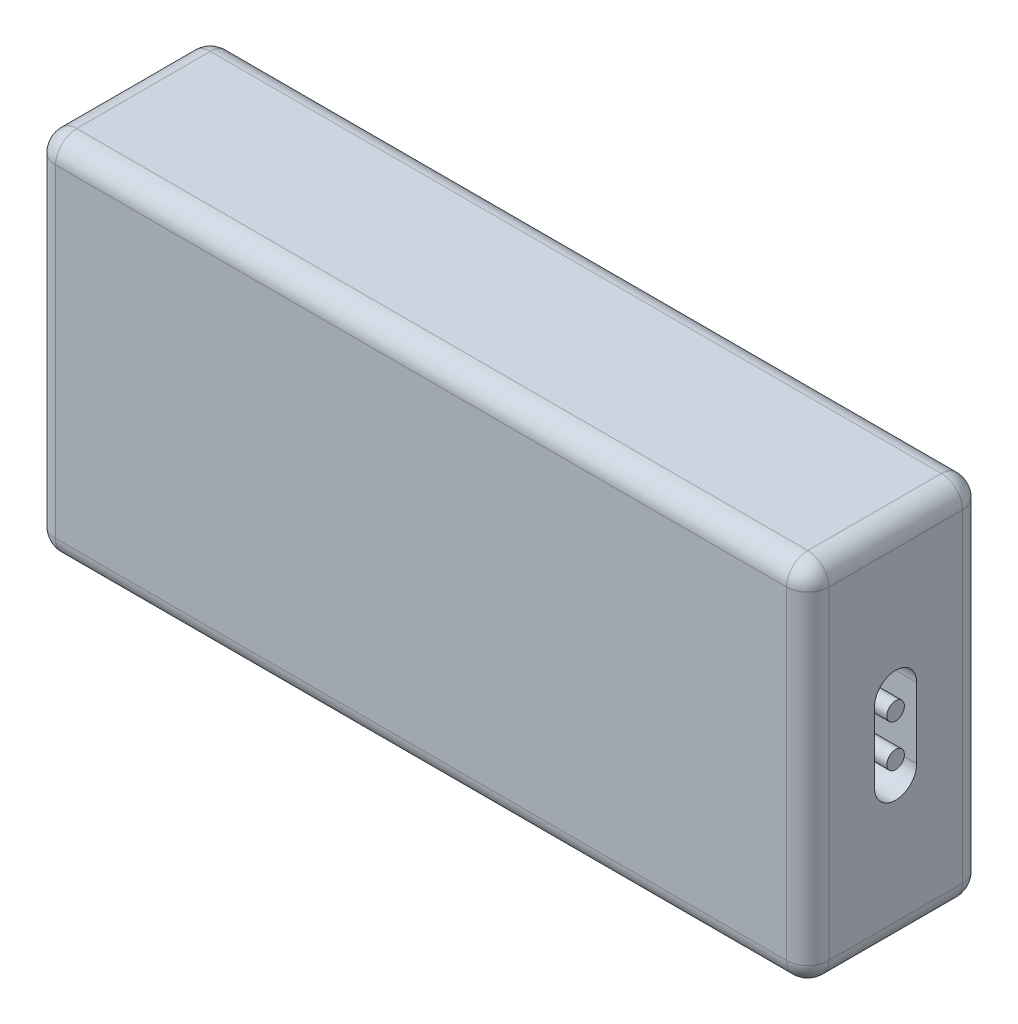
SolidWorks part; units mm, degrees
material "Резина"
ref_plane "Спереди" through (0, 0, 0) normal (0, 0, 1) x (1, 0, 0)
ref_plane "Сверху" through (0, 0, 0) normal (0, 1, 0) x (1, 0, 0)
ref_plane "Справа" through (0, 0, 0) normal (1, 0, 0) x (0, 0, -1)
sketch "Эскиз1" plane through (0, 0, 0) normal (0, 0, 1) x (1, 0, 0)
  line L0 (0, 0) -> (110, 0)
  line L1 (0, 0) -> (0, 52)
  line L2 (110, 0) -> (110, 52)
  line L3 (0, 52) -> (110, 52)
  dimension "D1" = 52
  dimension "D2" = 110
extrude "Бобышка-Вытянуть1" add sketch "Эскиз1" along normal blind 25
sketch "Эскиз2" plane through (110, 0, 0) normal (1, 0, 0) x (0, 0, -1)
  line L0 (-12.5, 0) -> (-12.5, 52) construction
  line L1 (-25, 0) -> (0, 0) construction
  line L2 (-25, 52) -> (0, 52) construction
  line L3 (0, 26) -> (-25, 26) construction
  line L4 (0, 0) -> (0, 52) construction
  line L5 (-25, 0) -> (-25, 52) construction
  line L6 (-12.5, 31) -> (-12.5, 21) construction
  line L7 (-9.5, 31) -> (-9.5, 21)
  line L8 (-15.5, 31) -> (-15.5, 21)
  arc A0 (-9.5, 31) -> (-15.5, 31) centre (-12.5, 31) ccw
  arc A1 (-15.5, 21) -> (-9.5, 21) centre (-12.5, 21) ccw
  circle A2 centre (-12.5, 29) radius 1.25
  circle A3 centre (-12.5, 23) radius 1.25
  point P14 (-12.5, 26)
  dimension "D3" = 2.5
  dimension "D4" = 3
  dimension "D5" = 3
  dimension "D1" = 6
  dimension "D2" = 10
extrude "Вырез-Вытянуть1" cut sketch "Эскиз2" against normal blind 6
sketch "Эскиз3" plane through (0, 0, 0) normal (-1, 0, 0) x (0, 0, 1)
  line L0 (12.5, 0) -> (12.5, 52) construction
  line L1 (25, 0) -> (0, 0) construction
  line L2 (25, 52) -> (0, 52) construction
  line L3 (0, 26) -> (25, 26) construction
  line L4 (0, 52) -> (0, 0) construction
  line L5 (25, 52) -> (25, 0) construction
  line L6 (10.5, 4) -> (14.5, 4)
  line L7 (10.5, 4) -> (10.5, 14)
  line L8 (14.5, 4) -> (14.5, 14)
  line L9 (10.5, 14) -> (14.5, 14)
  point P12 (12.5, 4)
  dimension "D1" = 10
  dimension "D2" = 4
  dimension "D3" = 4
extrude "Вырез-Вытянуть2" cut sketch "Эскиз3" against normal blind 6
sketch "Эскиз4" plane through (0, 0, 0) normal (-1, 0, 0) x (0, 0, 1)
  line L0 (0, 26) -> (25, 26) construction
  line L1 (0, 52) -> (0, 0) construction
  line L2 (25, 52) -> (25, 0) construction
  line L3 (12.5, 52) -> (12.5, 0) construction
  line L4 (25, 52) -> (0, 52) construction
  line L5 (25, 0) -> (0, 0) construction
  line L6 (10.5, 38) -> (14.5, 38)
  line L7 (10.5, 38) -> (10.5, 48)
  line L8 (14.5, 38) -> (14.5, 48)
  line L9 (10.5, 48) -> (14.5, 48)
  point P12 (12.5, 48)
  dimension "D1" = 10
  dimension "D2" = 4
  dimension "D3" = 4
extrude "Вырез-Вытянуть3" cut sketch "Эскиз4" against normal blind 6
sketch "Эскиз5" plane through (0, 0, 0) normal (0, 0, -1) x (-1, 0, 0)
  line L0 (-15, 5) -> (-32, 5)
  line L1 (-15, 5) -> (-15, 13)
  line L2 (-32, 5) -> (-32, 13)
  line L3 (-15, 13) -> (-32, 13)
  line L4 (0, 52) -> (0, 0) construction
  line L5 (0, 0) -> (-110, 0) construction
  dimension "D1" = 15
  dimension "D2" = 5
  dimension "D3" = 8
  dimension "D4" = 17
extrude "Вырез-Вытянуть4" cut sketch "Эскиз5" against normal blind 2
fillet "Скругление1" radius 3 12 edges at (0, 0, 12.5) (0, 52, 12.5) (0, 26, 25) (55, 0, 25) (110, 0, 12.5) (110, 26, 25) (110, 52, 12.5) (55, 52, 25) (0, 26, 0) (55, 0, 0) (110, 26, 0) (55, 52, 0)
